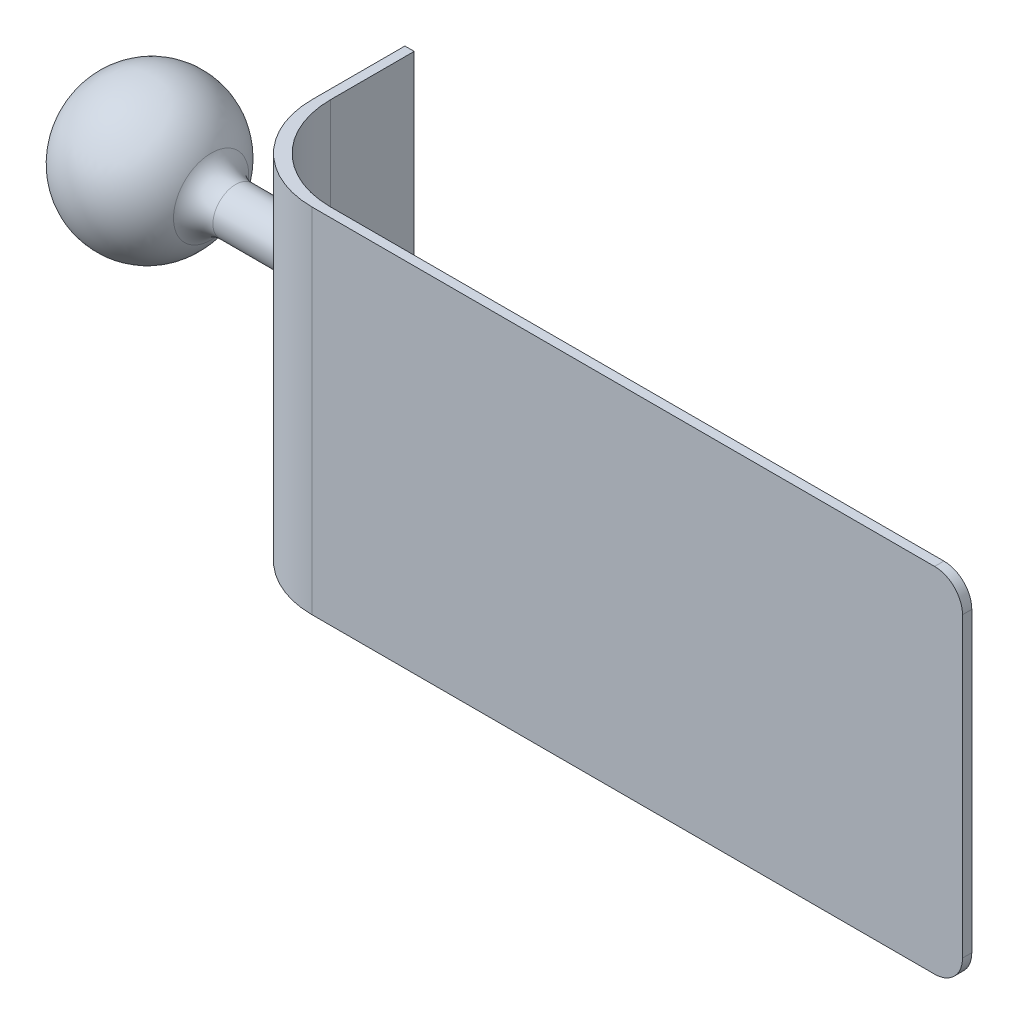
SolidWorks part; units mm, degrees
ref_plane "Front Plane" through (0, 0, 0) normal (0, 0, 1) x (1, 0, 0)
ref_plane "Top Plane" through (0, 0, 0) normal (0, 1, 0) x (1, 0, 0)
ref_plane "Right Plane" through (0, 0, 0) normal (1, 0, 0) x (0, 0, -1)
sketch "Sketch1" plane through (0, 0, 0) normal (0, 1, 0) x (1, 0, 0)
  line L0 (0, 0) -> (0, -19)
  line L1 (0, -19) -> (79, -19)
  line L2 (79, -19) -> (79, -20)
  line L3 (79, -20) -> (-1, -20)
  line L4 (-1, -20) -> (-1, 0)
  line L5 (-1, 0) -> (0, 0)
  dimension "D1" = 1
  dimension "D2" = 1
  dimension "D3" = 80
  dimension "D4" = 20
extrude "Boss-Extrude1" add sketch "Sketch1" along normal mid plane 38
fillet "Fillet1" radius 3 2 edges at (79, -19, 19.5) (79, 19, 19.5)
fillet "Fillet2" radius 10 2 edges at (-1, 0, 20) (0, 0, 19)
sketch "Sketch2" plane through (0, 0, 0) normal (0, 1, 0) x (1, 0, 0)
  line L0 (-0.7737, -3) -> (-15.7737, -3)
  line L1 (-0.5031, -5.4549) -> (-30.5031, -5.4549) construction
  line L2 (0, 0) -> (-1, 0) construction
  line L3 (-0.5031, -5.4549) -> (-0.5031, -3) construction
  line L4 (-0.5031, -3) -> (-0.7737, -3) construction
  line L5 (-0.5031, -5.4549) -> (-30.5031, -5.4549)
  line L6 (-0.7737, -3) -> (-0.5031, -5.4549)
  arc A0 (-30.5031, -5.4549) -> (-15.7737, -3) centre (-23.0216, -4.9282) cw
  dimension "D4" = 30
  dimension "D5" = 7.5
  dimension "D2" = 3
  dimension "D3" = 15
revolve "Revolve2" add sketch "Sketch2" angle 360 about L5
fillet "Fillet3" radius 3 2 edges at (-15.7737, 0, 3) (-1, 0, 3)
